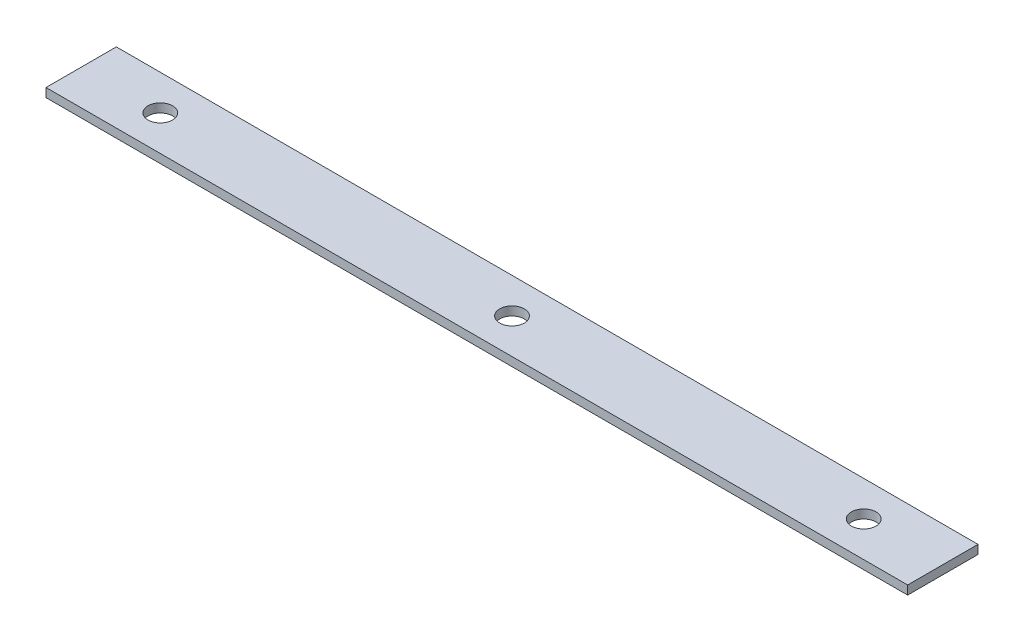
SolidWorks part; units mm, degrees
note: The reader was unsure of these and kept them because the rebuilt part matched: thickness of "Base-Flange1", "Sheet-Metal1", "Sheet-Metal2", "Sheet-Metal3", "Sheet-Metal4".
material "AISI 304"
ref_plane "Front Plane" through (0, 0, 0) normal (0, 0, 1) x (1, 0, 0)
ref_plane "Top Plane" through (0, 0, 0) normal (0, 1, 0) x (1, 0, 0)
ref_plane "Right Plane" through (0, 0, 0) normal (1, 0, 0) x (0, 0, -1)
sketch "Sketch1" plane through (0, 0, 0) normal (0, 1, 0) x (1, 0, 0)
  line L1 (-122.5, -10) -> (122.5, -10)
  line L2 (-122.5, -10) -> (-122.5, 10)
  line L3 (-122.5, 10) -> (122.5, 10)
  line L4 (122.5, -10) -> (122.5, 10)
  line L5 (-122.5, -10) -> (122.5, 10) construction
  line L6 (-122.5, 10) -> (122.5, -10) construction
  point P0 (0, 0)
  dimension "D1" = 20
  dimension "D2" = 245
base flange "Base-Flange1" sketch "Sketch1" thickness 2.5 reverse thickness direction no parameters "D1"=0
sketch "Sketch6" plane through (0, 0, 0) normal (0, 1, 0) x (1, 0, 0)
  circle A0 centre (0, 0) radius 3.5
  dimension "D1" = 7
extrude "Cut-Extrude1" cut sketch "Sketch6" against normal blind 10 normal cut yes
pattern_linear "LPattern1" count 6 spacing 146 along (-1, 0, 0) count 6 spacing 146 along (1, 0, 0) of "Cut-Extrude1"
pattern_linear "LPattern2" count 2 spacing 100 along (-1, 0, 0) count 2 spacing 100 along (1, 0, 0) of "Cut-Extrude1"
sketch "Bend-Lines1" [suppressed] plane through (0, 0, 0) normal (0, 1, 0) x (1, 0, 0)
sketch "Bounding-Box1" [suppressed] plane through (0, 0, 0) normal (0, 1, 0) x (1, 0, 0)
sheet metal parameters "Sheet-Metal1" thickness 2.5 parameters "D1"=0
flat pattern "Flat-Pattern1" [suppressed]
sketch "Bend-Lines2" plane through (0, 0, 0) normal (0, 1, 0) x (1, 0, 0)
sketch3d "Bounding-Box2" [suppressed]
  line L0 (-790, 10, 0) -> (790, 10, 0) construction
  line L1 (-790, -10, 0) -> (790, -10, 0) construction
  line L2 (-790, 10, 0) -> (-790, -10, 0) construction
  line L3 (790, 10, 0) -> (790, -10, 0) construction
sheet metal parameters "Sheet-Metal2" thickness 2.5 parameters "D1"=0, "D7"=2
flat pattern "Flat-Pattern1"
sketch "Bend-Lines2" plane through (0, 0, 0) normal (0, 1, 0) x (1, 0, 0)
sketch3d "Bounding-Box2" [suppressed]
  line L0 (790, 10, 0) -> (-790, 10, 0) construction
  line L1 (790, -10, 0) -> (-790, -10, 0) construction
  line L2 (790, 10, 0) -> (790, -10, 0) construction
  line L3 (-790, 10, 0) -> (-790, -10, 0) construction
sheet metal parameters "Sheet-Metal3" thickness 2.5 parameters "D1"=0, "D7"=2
flat pattern "Flat-Pattern1"
sketch "Bend-Lines2" plane through (0, 0, 0) normal (0, 1, 0) x (1, 0, 0)
sketch3d "Bounding-Box2" [suppressed]
  line L0 (122.5, 10, 0) -> (-122.5, 10, 0) construction
  line L1 (122.5, -10, 0) -> (-122.5, -10, 0) construction
  line L2 (122.5, 10, 0) -> (122.5, -10, 0) construction
  line L3 (-122.5, 10, 0) -> (-122.5, -10, 0) construction
sheet metal parameters "Sheet-Metal4" thickness 2.5 parameters "D1"=0, "D7"=2
flat pattern "Flat-Pattern1"
sketch "Bend-Lines2" plane through (0, 0, 0) normal (0, 1, 0) x (1, 0, 0)
sketch3d "Bounding-Box2" [suppressed]
  line L0 (122.5, 10, 0) -> (-122.5, 10, 0) construction
  line L1 (122.5, -10, 0) -> (-122.5, -10, 0) construction
  line L2 (122.5, 10, 0) -> (122.5, -10, 0) construction
  line L3 (-122.5, 10, 0) -> (-122.5, -10, 0) construction
